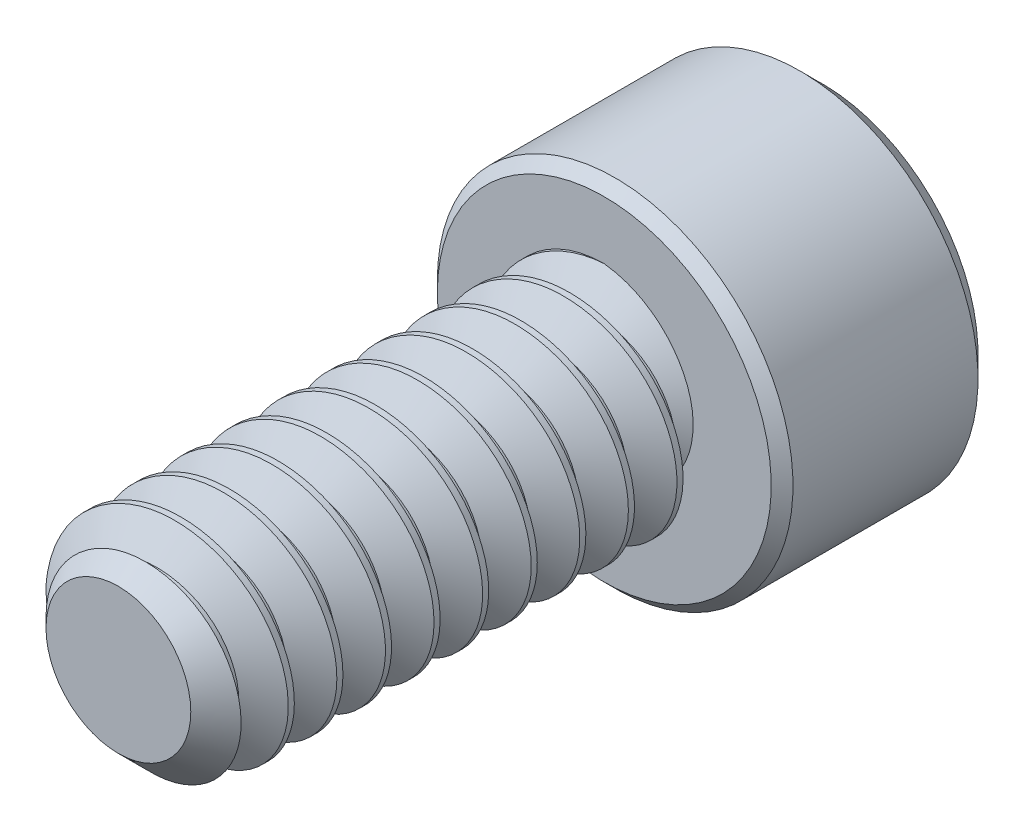
SolidWorks part; units mm, degrees
material "Plain Carbon Steel"
ref_plane "Front Plane" through (0, 0, 0) normal (0, 0, 1) x (1, 0, 0)
ref_plane "Top Plane" through (0, 0, 0) normal (0, 1, 0) x (1, 0, 0)
ref_plane "Right Plane" through (0, 0, 0) normal (1, 0, 0) x (0, 0, -1)
sketch "Sketch1" plane through (0, 0, 0) normal (0, 0, 1) x (1, 0, 0)
  line L0 (0, 1.4224) -> (0, -1.4224) construction
  circle A0 centre (0, 0) radius 1.4224
  dimension "OD" = 2.8448
extrude "Extrude1" add sketch "Sketch1" against normal blind 6.35
sketch "Sketch2" plane through (0, 0, 0) normal (0, 0, 1) x (1, 0, 0)
  circle A0 centre (0, 0) radius 1.4224 construction
  circle A1 centre (0, 0) radius 1.4224
curve "Helix/Spiral1" pitch 0.635 height 6.985 radius 1.4224 centre (0, 0, 0) axis (0, 0, -1) start towards (0, 1, 0) parameters "pitch"=0.635
chamfer "Chamfer3" distance 0.4763 angle 45 1 edges at (1.4224, 0, 0)
sketch "Sketch3" plane through (0, 0, 0) normal (1, 0, 0) x (0, 0, -1)
  line L0 (-0.5556, 1.4224) -> (-0.3175, 1.01)
  line L1 (-0.3175, 1.01) -> (-0.2381, 1.01)
  line L2 (-0.2381, 1.01) -> (0, 1.4224)
  line L3 (-0.5556, 1.4224) -> (0, 1.4224)
  line L4 (-0.2778, 1.4224) -> (-0.2778, 1.01) construction
  line L5 (-0.4366, 1.2162) -> (-0.1191, 1.2162) construction
  line L6 (0, 1.4224) -> (0, -1.4224) construction
  dimension "D1" = 0.0794
  dimension "D2" = 0.3175
  dimension "D3" = 60
sweep "Cut-Sweep1" cut profiles "Sketch3" path "Helix/Spiral1" align with end faces yes
sketch "Sketch6" plane through (0, 0, -6.35) normal (0, 0, -1) x (-1, 0, 0)
  circle A0 centre (0, 0) radius 2.3241
  dimension "head dia" = 4.6482
extrude "Extrude2" add sketch "Sketch6" along normal blind 2.8448
sketch "Sketch7" plane through (0, 0, -9.1948) normal (0, 0, -1) x (-1, 0, 0)
  line L1 (0, 1.3748) -> (-1.1906, 0.6874)
  line L2 (-1.1906, 0.6874) -> (-1.1906, -0.6874)
  line L3 (-1.1906, -0.6874) -> (0, -1.3748)
  line L4 (0, -1.3748) -> (1.1906, -0.6874)
  line L5 (1.1906, -0.6874) -> (1.1906, 0.6874)
  line L6 (1.1906, 0.6874) -> (0, 1.3748)
  circle A0 centre (0, 0) radius 1.1906 construction
  dimension "hex dia" = 2.3813
extrude "Cut-Extrude1" cut sketch "Sketch7" against normal blind 1.7859
sketch "Sketch8" plane through (0, 0, -9.1948) normal (0, 0, -1) x (-1, 0, 0)
  circle A0 centre (0, 0) radius 1.3748
extrude "Cut-Extrude2" cut sketch "Sketch8" against normal blind 0.2845 draft 45
chamfer "Chamfer1" distance 0.2845 angle 45 1 edges at (-2.3241, 0, -9.1948)
chamfer "Chamfer2" distance 0.1422 angle 45 1 edges at (-2.3241, 0, -6.35)
sketch "Sketch9" plane through (0, 0, 0) normal (1, 0, 0) x (0, 0, -1)
  line L0 (0, 1.4224) -> (0, -1.4224) construction
  line L1 (3.4925, 1.4224) -> (3.4925, -1.4224) construction
  line L2 (6.35, 2.3241) -> (6.35, -2.3241) construction
  line L3 (9.1948, 2.3241) -> (9.1948, -2.3241) construction
  line L4 (9.1948, 0) -> (0, 0) construction
  dimension "D1" = 3.4925
  dimension "D2" = 2.8448
  dimension "D3" = 4.6482
  dimension "D4" = 6.35
equation "\"D3@Helix/Spiral1\" = \"screw length@Extrude1\"+\"pitch@Helix/Spiral1\""
equation "\"D1@Sketch3\" = \"pitch@Helix/Spiral1\"*.125"
equation "\"D2@Sketch3\" = \"pitch@Helix/Spiral1\"*.5"
equation "\"D1@Cut-Extrude1\" = \"hex dia@Sketch7\"*.75"
equation "\"D1@Chamfer1\" = \"head depth@Extrude2\"/10"
equation "\"D1@Sketch9\" = \"pitch@Helix/Spiral1\"*5.5"
equation "\"D1@Chamfer2\" = \"D1@Chamfer1\"/2"
equation "\"D1@Cut-Extrude2\" = \"D1@Chamfer2\"*2"
equation "\"D1@Chamfer3\" = \"pitch@Helix/Spiral1\"*.750"
equation "\"D2@Sketch9\" = \"head depth@Extrude2\""
equation "\"D3@Sketch9\" = \"head dia@Sketch6\""
equation "\"D4@Sketch9\" = \"screw length@Extrude1\""
